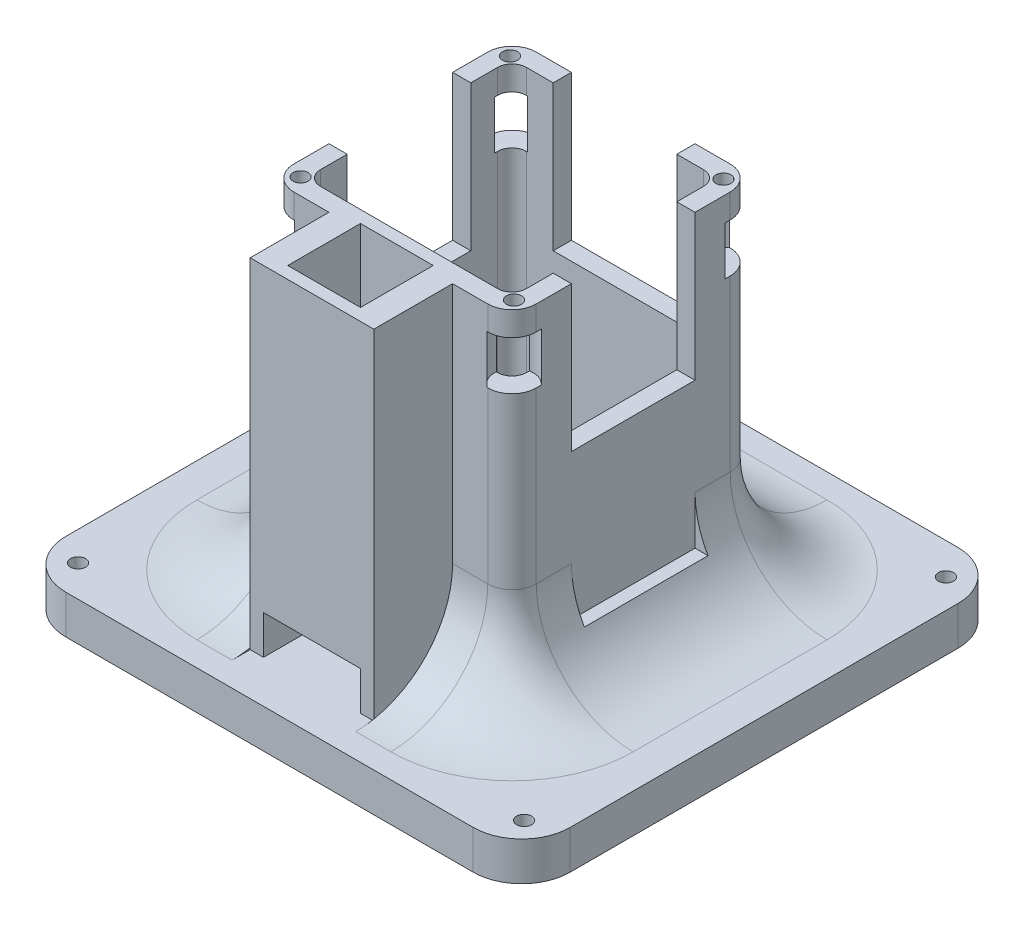
SolidWorks part; units mm, degrees
ref_plane "前视基准面" through (0, 0, 0) normal (0, 0, 1) x (1, 0, 0)
ref_plane "上视基准面" through (0, 0, 0) normal (0, 1, 0) x (1, 0, 0)
ref_plane "右视基准面" through (0, 0, 0) normal (1, 0, 0) x (0, 0, -1)
sketch "Sketch1" plane through (0, 0, 0) normal (0, 1, 0) x (1, 0, 0)
  line L1 (-52, -50) -> (52, -50)
  line L2 (-52, -50) -> (-52, 50)
  line L3 (-52, 50) -> (52, 50)
  line L4 (52, -50) -> (52, 50)
  line L5 (-52, -50) -> (52, 50) construction
  line L6 (-52, 50) -> (52, -50) construction
  point P0 (0, 0)
  dimension "D1" = 100
  dimension "D2" = 104
extrude "Boss-Extrude1" add sketch "Sketch1" along normal blind 8
fillet "Fillet1" radius 10 4 edges at (-52, 4, -50) (52, 4, -50) (52, 4, 50) (-52, 4, 50)
sketch "Sketch2" plane through (0, 8, 0) normal (0, 1, 0) x (1, 0, 0)
  line L0 (0, 50) -> (0, -50) construction
  line L1 (42, 50) -> (-42, 50) construction
  line L2 (-42, -50) -> (42, -50) construction
  line L3 (-52, 0) -> (52, 0) construction
  line L4 (-52, 40) -> (-52, -40) construction
  line L5 (52, -40) -> (52, 40) construction
  circle A0 centre (-46, 43.5) radius 1.55
  circle A1 centre (46, 43.5) radius 1.55
  circle A2 centre (46, -43.5) radius 1.55
  circle A3 centre (-46, -43.5) radius 1.55
  dimension "D1" = 3.1
  dimension "D2" = 46
  dimension "D3" = 43.5
  dimension "D4" = 46
  dimension "D5" = 43.5
  dimension "D6" = 46
  dimension "D7" = 43.5
  dimension "D8" = 43.5
  dimension "D9" = 46
extrude "Cut-Extrude1" cut sketch "Sketch2" against normal blind 10
sketch "Sketch3" plane through (0, 8, 0) normal (0, 1, 0) x (1, 0, 0)
  line L1 (-21.25, -21.25) -> (21.25, -21.25)
  line L2 (-21.25, -21.25) -> (-21.25, 21.25)
  line L3 (-21.25, 21.25) -> (21.25, 21.25)
  line L4 (21.25, -21.25) -> (21.25, 21.25)
  line L5 (-21.25, -21.25) -> (21.25, 21.25) construction
  line L6 (-21.25, 21.25) -> (21.25, -21.25) construction
  line L7 (-25, -25) -> (25, -25)
  line L8 (-25, -25) -> (-25, 25)
  line L9 (-25, 25) -> (25, 25)
  line L10 (25, -25) -> (25, 25)
  line L11 (-25, -25) -> (25, 25) construction
  line L12 (-25, 25) -> (25, -25) construction
  point P0 (0, 0)
  point P5 (0, 0)
  dimension "D1" = 42.5
  dimension "D2" = 42.5
  dimension "D3" = 50
  dimension "D4" = 50
extrude "Boss-Extrude2" add sketch "Sketch3" along normal blind 70
fillet "Fillet2" radius 5 4 edges at (-25, 43, -25) (25, 43, -25) (25, 43, 25) (-25, 43, 25)
fillet "Fillet3" radius 3 4 edges at (-21.25, 43, 21.25) (21.25, 43, 21.25) (21.25, 43, -21.25) (-21.25, 43, -21.25)
sketch "Sketch4" plane through (0, 78, 0) normal (0, 1, 0) x (1, 0, 0)
  line L0 (20, 25) -> (-20, 25) construction
  line L1 (-12.75, 25) -> (12.75, 25)
  line L2 (-12.75, 25) -> (-12.75, 21.25)
  line L3 (-12.75, 21.25) -> (12.75, 21.25)
  line L4 (12.75, 25) -> (12.75, 21.25)
  line L5 (18.25, 21.25) -> (-18.25, 21.25) construction
  line L6 (-21.25, 18.25) -> (-21.25, -18.25) construction
  line L7 (-25, 20) -> (-25, -20) construction
  line L8 (-25, 12.75) -> (-21.25, 12.75)
  line L9 (-25, 12.75) -> (-25, -12.75)
  line L10 (-25, -12.75) -> (-21.25, -12.75)
  line L11 (-21.25, 12.75) -> (-21.25, -12.75)
  line L12 (-21.25, 18.25) -> (-21.25, -18.25) construction
  line L13 (-18.25, -21.25) -> (18.25, -21.25) construction
  dimension "D1" = 25.5
  dimension "D2" = 8.5
  dimension "D3" = 25.5
  dimension "D4" = 8.5
extrude "Cut-Extrude2" cut sketch "Sketch4" against normal blind 70
mirror "Mirror1" about plane through (0, 0, 0) normal (0, 0, 1) of "Cut-Extrude2"
mirror "Mirror2" about plane through (0, 0, 0) normal (1, 0, 0) of "Cut-Extrude2"
sketch "Sketch5" plane through (0, 78, 0) normal (0, 1, 0) x (1, 0, 0)
  line L0 (-12.75, 25) -> (-20, 25) construction
  line L2 (-25, 20) -> (-25, 12.75) construction
  circle A0 centre (-22, 21.6) radius 1.55
  dimension "D1" = 3.1
  dimension "D2" = 3.4
  dimension "D3" = 3
extrude "Cut-Extrude3" cut sketch "Sketch5" against normal blind 5
sketch "Sketch6" plane through (0, 73, 0) normal (0, 1, 0) x (1, 0, 0)
  circle A0 centre (-22, 21.6) radius 4
  dimension "D1" = 8
extrude "Cut-Extrude4" cut sketch "Sketch6" against normal blind 10
mirror "Mirror3" about plane through (0, 0, 0) normal (1, 0, 0) of "Cut-Extrude3", "Cut-Extrude4"
mirror "Mirror4" about plane through (0, 0, 0) normal (0, 0, 1) of "Mirror3"
sketch "Sketch7" plane through (0, 8, 0) normal (0, 1, 0) x (1, 0, 0)
  line L1 (-12.75, 25) -> (12.75, 25)
  line L2 (-12.75, 25) -> (-12.75, 21.25)
  line L3 (-12.75, 21.25) -> (12.75, 21.25)
  line L4 (12.75, 25) -> (12.75, 21.25)
  line L5 (-25, 12.75) -> (-21.25, 12.75)
  line L6 (-25, 12.75) -> (-25, -12.75)
  line L7 (-25, -12.75) -> (-21.25, -12.75)
  line L8 (-21.25, 12.75) -> (-21.25, -12.75)
  line L9 (21.25, 12.75) -> (25, 12.75)
  line L10 (21.25, 12.75) -> (21.25, -12.75)
  line L11 (21.25, -12.75) -> (25, -12.75)
  line L12 (25, 12.75) -> (25, -12.75)
extrude "Boss-Extrude3" add sketch "Sketch7" along normal blind 10
fillet "Fillet4" radius 20 9 edges at (16.375, 8, 25) (23.5355, 8, 23.5355) (25, 8, 0) (23.5355, 8, -23.5355) (0, 8, -25) (-23.5355, 8, -23.5355) (-16.375, 8, 25) (-23.5355, 8, 23.5355) (-25, 8, 0)
sketch "Sketch8" plane through (0, 18, 0) normal (0, 1, 0) x (1, 0, 0)
  line L13 (-25, 12.75) -> (-21.25, 12.75)
  line L14 (-25, 12.75) -> (-25, -12.75)
  line L15 (-25, -12.75) -> (-21.25, -12.75)
  line L16 (-21.25, 12.75) -> (-21.25, -12.75)
  line L17 (-12.75, 21.25) -> (12.75, 21.25)
  line L18 (-12.75, 21.25) -> (-12.75, 25)
  line L19 (-12.75, 25) -> (12.75, 25)
  line L20 (12.75, 21.25) -> (12.75, 25)
  line L21 (21.25, 12.75) -> (25, 12.75)
  line L22 (21.25, 12.75) -> (21.25, -12.75)
  line L23 (21.25, -12.75) -> (25, -12.75)
  line L24 (25, 12.75) -> (25, -12.75)
extrude "Boss-Extrude4" add sketch "Sketch8" along normal blind 30
sketch "Sketch9" plane through (0, 8, 0) normal (0, 1, 0) x (1, 0, 0)
  line L0 (12.75, -21.25) -> (12.75, -45) construction
  line L1 (-12.75, -21.25) -> (12.75, -21.25)
  line L2 (-12.75, -21.25) -> (-12.75, -41.25)
  line L3 (-12.75, -41.25) -> (12.75, -41.25)
  line L4 (12.75, -21.25) -> (12.75, -41.25)
  dimension "D1" = 20
extrude "Boss-Extrude5" add sketch "Sketch9" along normal up to surface (70 mm away) up to face at (22, 78, 20.05)
sketch "Sketch10" plane through (0, 0, 41.25) normal (0, 0, 1) x (1, 0, 0)
  line L0 (-12.75, 8) -> (12.75, 8) construction
  line L1 (-10, 8) -> (10, 8)
  line L2 (-10, 8) -> (-10, 16)
  line L3 (-10, 16) -> (10, 16)
  line L4 (10, 8) -> (10, 16)
  line L5 (12.75, 78) -> (12.75, 8.3547) construction
  dimension "D1" = 20
  dimension "D2" = 2.75
  dimension "D3" = 8
extrude "Cut-Extrude5" cut sketch "Sketch10" against normal blind 30
sketch "Sketch11" plane through (0, 78, 0) normal (0, 1, 0) x (1, 0, 0)
  line L0 (12.75, -25) -> (12.75, -41.25) construction
  line L1 (-7.5, -38.75) -> (7.5, -38.75)
  line L2 (-7.5, -38.75) -> (-7.5, -23.75)
  line L3 (-7.5, -23.75) -> (7.5, -23.75)
  line L4 (7.5, -38.75) -> (7.5, -23.75)
  line L5 (-7.5, -38.75) -> (7.5, -23.75) construction
  line L6 (-7.5, -23.75) -> (7.5, -38.75) construction
  line L8 (12.75, -41.25) -> (-12.75, -41.25) construction
  point P0 (0, -31.25)
  dimension "D1" = 15
  dimension "D2" = 15
  dimension "D3" = 5.25
  dimension "D4" = 2.5
extrude "Cut-Extrude6" cut sketch "Sketch11" against normal blind 70
